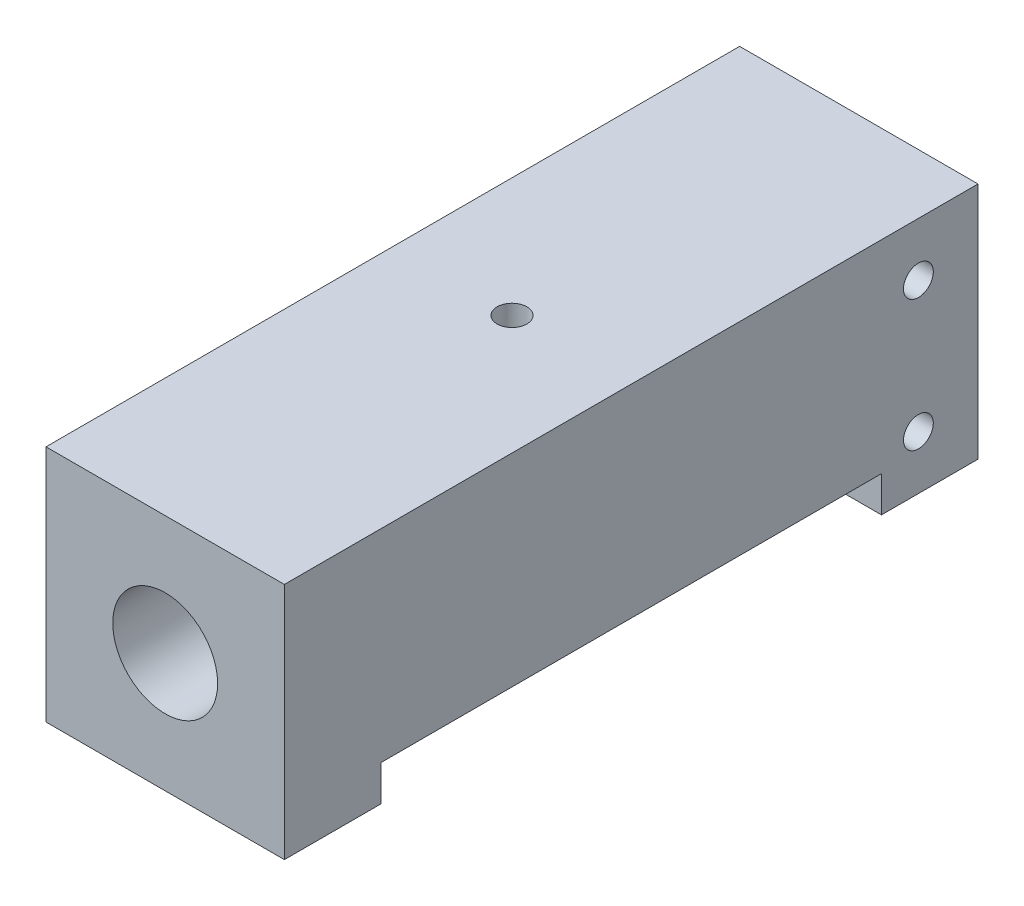
SolidWorks part; units mm, degrees
material "6063-T5"
ref_plane "Piano frontale" through (0, 0, 0) normal (0, 0, 1) x (1, 0, 0)
ref_plane "Piano superiore" through (0, 0, 0) normal (0, 1, 0) x (1, 0, 0)
ref_plane "Piano destro" through (0, 0, 0) normal (1, 0, 0) x (0, 0, -1)
sketch "Schizzo1" plane through (0, 0, 0) normal (0, 0, 1) x (1, 0, 0)
  line L1 (10, -10) -> (-10, -10)
  line L2 (10, -10) -> (10, 10)
  line L3 (10, 10) -> (-10, 10)
  line L4 (-10, -10) -> (-10, 10)
  line L5 (10, -10) -> (-10, 10) construction
  line L6 (10, 10) -> (-10, -10) construction
  point P0 (0, 0)
  dimension "D1" = 20
  dimension "D2" = 20
extrude "Estrusione-Estrusione1" add sketch "Schizzo1" against normal blind 58.2
sketch "Schizzo2" plane through (0, 0, -58.2) normal (0, 0, -1) x (-1, 0, 0)
  circle A0 centre (0, 0) radius 3
  dimension "D1" = 6
extrude "Taglio-Estrusione1" cut sketch "Schizzo2" against normal through all
sketch "Schizzo3" plane through (0, 0, -58.2) normal (0, 0, -1) x (-1, 0, 0)
  point P0 (0, 0)
hole_wizard "Foro filettato G1/8-1" positions "Schizzo8" profile "Schizzo7" tap size "G1/8" standard "BSI"
sketch "Schizzo8" plane through (0, 0, 0) normal (0, 0, 1) x (1, 0, 0)
  point P0 (0, 0)
sketch "Schizzo7" plane through (0, 0, 0) normal (1, 0, 0) x (0, -1, 0)
  line L0 (0, 0) -> (0, 12.6438)
  line L1 (0, 12.6438) -> (4.4, 10)
  line L2 (4.4, 10) -> (4.4, 0)
  line L5 (4.4, 0) -> (0, 0)
  line L10 (0, 12.6438) -> (-4.4, 10) construction
  line L11 (0, -6.35) -> (0, 107.95) construction
  dimension "Tap Drill Dia." = 8.8
  dimension "Tap Drill Depth" = 10
  dimension "Drill Angle" = 118
sketch "Schizzo11" plane through (0, 10, 0) normal (0, 1, 0) x (1, 0, 0)
  line L0 (0, 58.2) -> (0, 0) construction
  line L1 (10, 58.2) -> (-10, 58.2) construction
  line L2 (10, 29.1) -> (-10, 29.1) construction
  line L3 (10, 58.2) -> (10, 0) construction
  point P10 (0, 29.1)
  point P11 (0, 29.1)
  point P12 (0, 29.1)
hole_wizard "M3 Tapped Hole2" positions "Schizzo3D1" profile "Schizzo12" tap size "M3" standard "DIN"
sketch3d "Schizzo3D1"
  point P0 (0, 10, -29.1)
sketch "Schizzo12" plane through (0, 10, -29.1) normal (1, 0, 0) x (0, 0, 1)
  line L0 (0, 0) -> (0, 5.7511)
  line L1 (0, 5.7511) -> (1.25, 5)
  line L2 (1.25, 5) -> (1.25, 0)
  line L5 (1.25, 0) -> (0, 0)
  line L10 (0, 5.7511) -> (-1.25, 5) construction
  line L11 (0, -6.35) -> (0, 107.95) construction
  dimension "Tap Drill Dia." = 2.5
  dimension "Tap Drill Depth" = 5
  dimension "Drill Angle" = 118
cosmetic thread "Hole Thread4" parameters "D1"=5, "D2"=3
hole_wizard "Foro Ø16.0 (16)-1" positions "Schizzo3D3" profile "Schizzo14" hole size "Ø16.0" standard "ISO"
sketch3d "Schizzo3D3"
  point P0 (0, 0, 0)
  point P3 (0, 0, -58.2)
sketch "Schizzo14" plane through (0, 0, -58.2) normal (1, 0, 0) x (0, 1, 0)
  line L0 (0, 0) -> (0, 16.8069)
  line L1 (0, 16.8069) -> (8, 12)
  line L2 (8, 12) -> (8, 0)
  line L5 (8, 0) -> (0, 0)
  line L10 (0, 16.8069) -> (-8, 12) construction
  line L11 (0, -6.35) -> (0, 107.95) construction
  dimension "Hole Dia." = 16
  dimension "Hole Depth" = 12
  dimension "Drill Angle" = 118
sketch "Schizzo15" plane through (10, 0, 0) normal (1, 0, 0) x (0, 0, -1)
  line L0 (46.2, 0) -> (58.2, 0) construction
  line L1 (46.2, 8) -> (46.2, -8) construction
  line L4 (58.2, -10) -> (58.2, 10) construction
  line L6 (58.2, -10) -> (0, -10) construction
  point P5 (53.2, -5.5)
  point P8 (53.2, 5.5)
  dimension "D1" = 5.5
  dimension "D2" = 7
  dimension "D3" = 5
  dimension "D4" = 4.5
hole_wizard "M3 Tapped Hole3" positions "Schizzo3D4" profile "Schizzo16" tap size "M3" standard "ISO" end condition through all
sketch3d "Schizzo3D4"
  point P0 (10, 5.5, -53.2)
  point P3 (10, -5.5, -53.2)
sketch "Schizzo16" plane through (10, 5.5, -53.2) normal (0, 1, 0) x (0, 0, -1)
  line L0 (0, 0) -> (0, 20)
  line L1 (0, 20) -> (1.25, 20)
  line L2 (1.25, 20) -> (1.25, 0)
  line L5 (1.25, 0) -> (0, 0)
  line L11 (0, -6.35) -> (0, 107.95) construction
  dimension "Thread Major Dia." = 2.5
  dimension "Thru Tap Drill Depth" = 20
sketch "Sketch1" plane through (-10, 0, 0) normal (-1, 0, 0) x (0, 0, 1)
  line L0 (-58.2, 10) -> (-58.2, -10) construction
  line L1 (-58.2, 3) -> (-22, 3)
  line L2 (-58.2, 3) -> (-58.2, -3)
  line L3 (-58.2, -3) -> (-22, -3)
  line L4 (-22, 3) -> (-22, -3)
  line L5 (0, 10) -> (0, -10) construction
  line L6 (0, 0) -> (-22, 0) construction
  point P8 (-22, 0)
  dimension "D1" = 6
  dimension "D2" = 22
extrude "Boss-Extrude1" add sketch "Sketch1" along normal blind 4.9
sketch "Sketch2" plane through (10, 0, 0) normal (1, 0, 0) x (0, 0, -1)
  line L0 (58.2, -10) -> (0, -10) construction
  line L1 (50.1, -10) -> (34.1, -10)
  line L2 (50.1, -10) -> (50.1, -7)
  line L3 (50.1, -7) -> (34.1, -7)
  line L4 (34.1, -7) -> (8.1, -7)
  line L5 (42.1, -7) -> (42.1, -12.5) construction
  line L6 (8.1, -7) -> (8.1, -10)
  line L7 (8.1, -10) -> (34.1, -10)
  line L8 (0, -10) -> (8.1, -10) construction
  line L9 (50.1, -10) -> (58.2, -10) construction
  dimension "D1" = 16
  dimension "D2" = 3
extrude "Cut-Extrude1" cut sketch "Sketch2" against normal through all
sketch "Sketch3" plane through (0, 0, -22) normal (0, 0, 1) x (1, 0, 0)
  point P0 (-13, 0)
hole_wizard "M3 Tapped Hole4" positions "Sketch6" profile "Sketch7" tap size "M3" standard "ISO"
sketch "Sketch6" plane through (0, 0, -22) normal (0, 0, 1) x (1, 0, 0)
  point P0 (-13, 0)
sketch "Sketch7" plane through (-13, 0, -22) normal (1, 0, 0) x (0, -1, 0)
  line L0 (0, 0) -> (0, 20.7511)
  line L1 (0, 20.7511) -> (1.25, 20)
  line L2 (1.25, 20) -> (1.25, 0)
  line L5 (1.25, 0) -> (0, 0)
  line L10 (0, 20.7511) -> (-1.25, 20) construction
  line L11 (0, -6.35) -> (0, 107.95) construction
  dimension "Tap Drill Dia." = 2.5
  dimension "Tap Drill Depth" = 20
  dimension "Drill Angle" = 118
